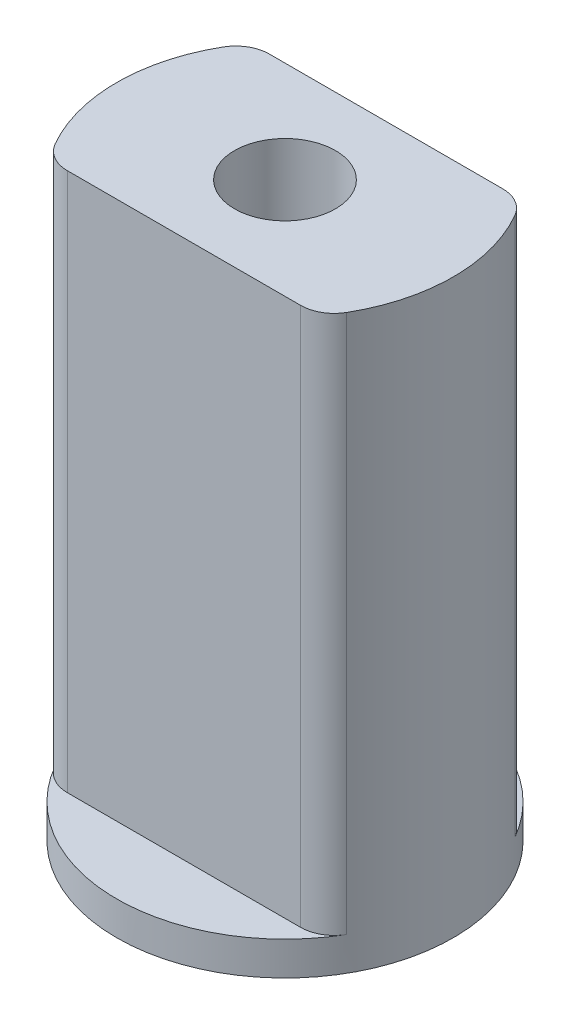
SolidWorks part; units mm, degrees
ref_plane "Front Plane" through (0, 0, 0) normal (0, 0, 1) x (1, 0, 0)
ref_plane "Top Plane" through (0, 0, 0) normal (0, 1, 0) x (1, 0, 0)
ref_plane "Right Plane" through (0, 0, 0) normal (1, 0, 0) x (0, 0, -1)
sketch "Sketch2" plane through (0, 0, 0) normal (0, 1, 0) x (1, 0, 0)
  circle A0 centre (0, 0) radius 2.5
  dimension "D1" = 5
extrude "Boss-Extrude1" add sketch "Sketch2" along normal blind 0.5
sketch "Sketch3" plane through (0, 0.5, 0) normal (0, 1, 0) x (1, 0, 0)
  line L0 (-2, 1.5) -> (2, 1.5)
  line L1 (-2.5, 0) -> (2.5, 0) construction
  line L2 (-2, -1.5) -> (2, -1.5)
  circle A0 centre (0, 0) radius 0.75
  circle A1 centre (0, 0) radius 2.5
  circle A2 centre (0, 0) radius 2.5
  circle M2 centre (0, 0) radius 2.5
  dimension "D3" = 1.5
  dimension "D2" = 1.5
  dimension "D1" = 0
extrude "Boss-Extrude2" add sketch "Sketch3" along normal blind 8 contours L1 A0 A2 L0 M2 | L1 A2 L2 A0 M2 region at (0, 0.5, -0.7823) region at (0, 0.5, 0.7823)
fillet "Fillet1" radius 0.5 4 edges
